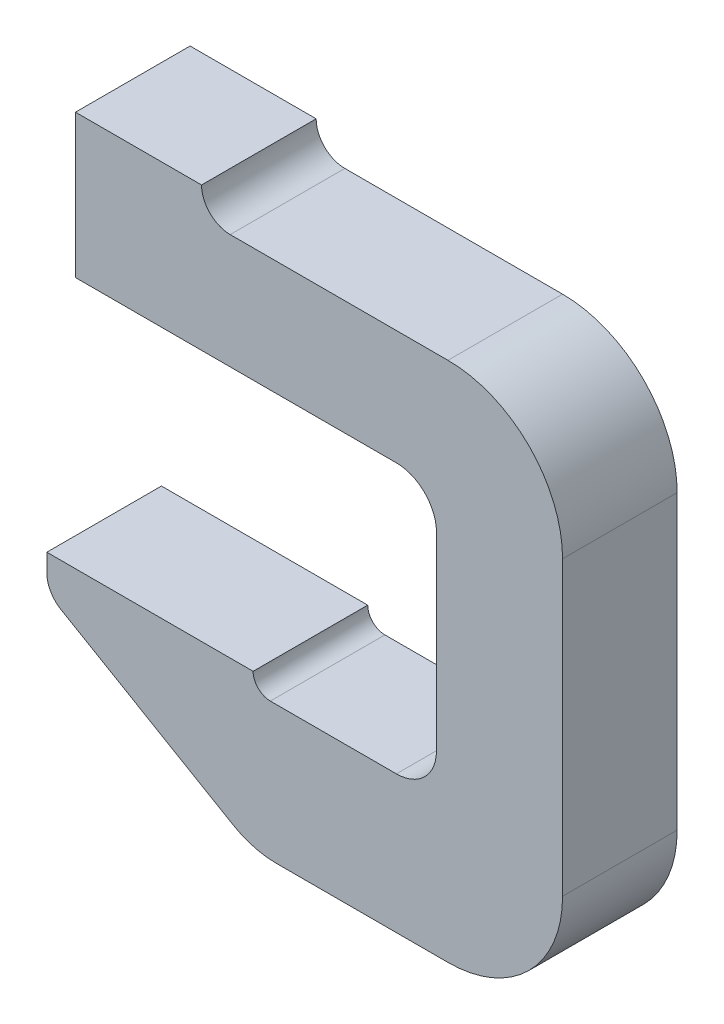
SolidWorks part; units mm, degrees
ref_plane "Plano frontal" through (0, 0, 0) normal (0, 0, 1) x (1, 0, 0)
ref_plane "Plano superior" through (0, 0, 0) normal (0, 1, 0) x (1, 0, 0)
ref_plane "Plano direito" through (0, 0, 0) normal (1, 0, 0) x (0, 0, -1)
sketch "Esboço1" plane through (0, 0, 0) normal (0, 0, 1) x (1, 0, 0)
  line L0 (0, 0) -> (0, 910)
  line L1 (0, 910) -> (-630, 910)
  line L2 (-630, 910) -> (-630, 960)
  line L3 (-630, 960) -> (-850, 960)
  line L4 (-850, 960) -> (-850, 710)
  line L5 (-850, 710) -> (-220, 710)
  line L6 (-220, 710) -> (-220, 240)
  line L7 (-220, 240) -> (-540, 240)
  line L8 (-540, 240) -> (-540, 270)
  line L9 (-540, 270) -> (-900, 270)
  line L10 (-900, 270) -> (-900, 210)
  line L11 (-900, 210) -> (-540, 0)
  line L12 (-540, 0) -> (0, 0)
extrude "Ressalto-extrusão1" add sketch "Esboço1" along normal blind 200
fillet "Filete1" radius 200 1 edges at (0, 910, 100)
fillet "Filete2" radius 200 1 edges at (0, 0, 100)
fillet "Filete3" radius 70 1 edges at (-220, 710, 100)
fillet "Filete4" radius 70 1 edges at (-220, 240, 100)
fillet "Filete5" radius 30 1 edges at (-540, 240, 100)
fillet "Filete6" radius 50 1 edges at (-630, 910, 100)
fillet "Filete7" radius 50 1 edges at (-900, 210, 100)
fillet "Filete8" radius 150 1 edges at (-540, 0, 100)
